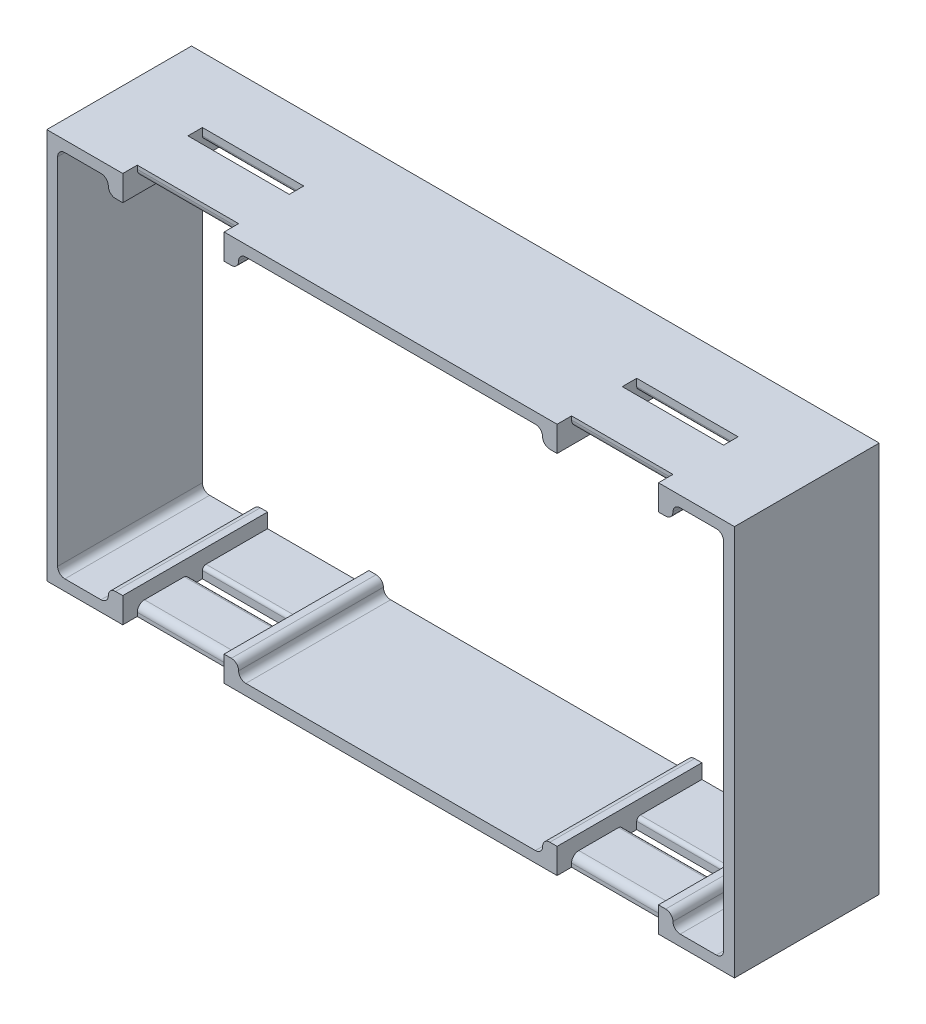
SolidWorks part; units mm, degrees
ref_plane "Front Plane" through (0, 0, 0) normal (0, 0, 1) x (1, 0, 0)
ref_plane "Top Plane" through (0, 0, 0) normal (0, 1, 0) x (1, 0, 0)
ref_plane "Right Plane" through (0, 0, 0) normal (1, 0, 0) x (0, 0, -1)
sketch "Sketch1" plane through (0, 0, 0) normal (0, 0, 1) x (1, 0, 0)
  line L0 (0, 0) -> (0, 15.5142) construction
  line L1 (0, 0) -> (24.8039, 0) construction
  line L2 (-46, 25.5) -> (46, 25.5)
  line L7 (46, 25.5) -> (46, -25.5)
  line L8 (-46, -25.5) -> (46, -25.5)
  line L9 (-46, 25.5) -> (-46, -25.5)
  line L10 (-47.5, 27) -> (47.5, 27)
  line L11 (47.5, 27) -> (47.5, -27)
  line L12 (-47.5, -27) -> (47.5, -27)
  line L13 (-47.5, 27) -> (-47.5, -27)
extrude "Boss-Extrude1" add sketch "Sketch1" along normal blind 20
sketch "Sketch2" plane through (0, 0, 0) normal (0, 0, -1) x (-1, 0, 0)
  line L0 (0, 0) -> (0, 13.0209) construction
  line L1 (0, 0) -> (7.1699, 0) construction
  line L3 (23, 25.5) -> (21, 25.5)
  line L4 (23, 25.5) -> (23, 23.5)
  line L5 (23, 23.5) -> (21, 23.5)
  line L6 (21, 25.5) -> (21, 23.5)
  line L7 (-37, 23.5) -> (-39, 23.5)
  line L8 (37, 25.5) -> (39, 25.5)
  line L9 (37, 25.5) -> (37, 23.5)
  line L10 (37, 23.5) -> (39, 23.5)
  line L11 (39, 25.5) -> (39, 23.5)
  line L12 (-39, 25.5) -> (-39, 23.5)
  line L13 (-37, 25.5) -> (-39, 25.5)
  line L14 (-37, 25.5) -> (-37, 23.5)
  line L15 (-23, 23.5) -> (-21, 23.5)
  line L16 (-21, 25.5) -> (-21, 23.5)
  line L17 (-23, 25.5) -> (-21, 25.5)
  line L18 (-23, 25.5) -> (-23, 23.5)
  line L19 (37, -23.5) -> (39, -23.5)
  line L20 (39, -25.5) -> (39, -23.5)
  line L21 (37, -25.5) -> (39, -25.5)
  line L22 (37, -25.5) -> (37, -23.5)
  line L23 (23, -23.5) -> (21, -23.5)
  line L24 (21, -25.5) -> (21, -23.5)
  line L25 (23, -25.5) -> (21, -25.5)
  line L26 (23, -25.5) -> (23, -23.5)
  line L27 (-23, -25.5) -> (-23, -23.5)
  line L28 (-23, -25.5) -> (-21, -25.5)
  line L29 (-21, -25.5) -> (-21, -23.5)
  line L30 (-23, -23.5) -> (-21, -23.5)
  line L31 (-37, -25.5) -> (-37, -23.5)
  line L32 (-37, -25.5) -> (-39, -25.5)
  line L33 (-39, -25.5) -> (-39, -23.5)
  line L34 (-37, -23.5) -> (-39, -23.5)
  line L35 (-46, 25.5) -> (46, 25.5) construction
  point P8 (0, 0)
  point P38 (0, 0)
  dimension "D1" = 2
  dimension "D2" = 2
  dimension "D3" = 2
  dimension "D4" = 2
  dimension "D5" = 14
  dimension "D6" = 37
extrude "Boss-Extrude2" add sketch "Sketch2" against normal blind 20
fillet "Fillet1" radius 1 20 edges at (-46, -25.5, 10) (-46, 25.5, 10) (46, -25.5, 10) (39, -25.5, 10) (39, -23.5, 10) (21, -23.5, 10) (21, -25.5, 10) (-21, -25.5, 10) (-21, -23.5, 10) (-39, -23.5, 10) (-39, -25.5, 10) (-39, 25.5, 10) (-39, 23.5, 10) (-21, 23.5, 10) (-21, 25.5, 10) (21, 25.5, 10) (21, 23.5, 10) (39, 23.5, 10) (39, 25.5, 10) (46, 25.5, 10)
sketch "Sketch3" plane through (0, -27, 0) normal (0, -1, 0) x (1, 0, 0)
  line L0 (0, 0) -> (0, 20) construction
  line L1 (-37, 11) -> (-23, 11)
  line L2 (-37, 11) -> (-37, 9)
  line L3 (-37, 9) -> (-23, 9)
  line L4 (-23, 11) -> (-23, 9)
  line L6 (37, 9) -> (23, 9)
  line L7 (23, 11) -> (23, 9)
  line L8 (37, 11) -> (23, 11)
  line L9 (37, 11) -> (37, 9)
  line L10 (37, 18) -> (23, 18)
  line L11 (-37, 20) -> (-23, 20)
  line L12 (-37, 20) -> (-37, 18)
  line L13 (-37, 18) -> (-23, 18)
  line L14 (-23, 20) -> (-23, 18)
  line L15 (23, 20) -> (23, 18)
  line L16 (37, 20) -> (23, 20)
  line L17 (37, 20) -> (37, 18)
  line L18 (-47.5, 20) -> (47.5, 20) construction
  point P7 (0, 0)
  point P22 (0, 20)
  point P23 (0, 0)
  point P24 (-23.2487, 18)
  dimension "D1" = 14
  dimension "D2" = 37
  dimension "D3" = 2
  dimension "D4" = 7
  dimension "D5" = 2
extrude "Cut-Extrude1" cut sketch "Sketch3" against normal through all both and the other way through all
fillet "Fillet2" radius 1 4 edges at (30, 25.5, 18) (30, -25.5, 18) (-30, -25.5, 18) (-30, 25.5, 18)
fillet "Fillet3" radius 0.5 8 edges at (30, 25.5, 9) (30, 25.5, 11) (-30, 25.5, 9) (-30, 25.5, 11) (-30, -25.5, 11) (-30, -25.5, 9) (30, -25.5, 11) (30, -25.5, 9)
